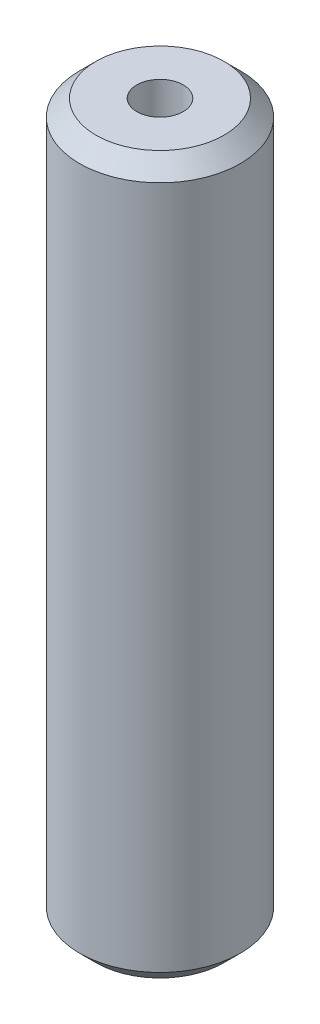
SolidWorks part; units mm, degrees
ref_plane "Front Plane" through (0, 0, 0) normal (0, 0, 1) x (1, 0, 0)
ref_plane "Top Plane" through (0, 0, 0) normal (0, 1, 0) x (1, 0, 0)
ref_plane "Right Plane" through (0, 0, 0) normal (1, 0, 0) x (0, 0, -1)
sketch "Sketch1" plane through (0, 0, 0) normal (0, 1, 0) x (1, 0, 0)
  circle A0 centre (0, 0) radius 5
  dimension "SHAFT_OD" = 10
extrude "Boss-Extrude1" add sketch "Sketch1" along normal blind 44.5572
sketch "Sketch2" plane through (0, 0, 0) normal (0, 1, 0) x (1, 0, 0)
  circle A0 centre (0, 0) radius 1.4435
  dimension "BORE_D" = 2.887
extrude "Cut-Extrude1" cut sketch "Sketch2" along normal through all
chamfer "Chamfer1" distance 1.0191 angle 45 2 edges at (0, 44.5572, 5) (0, 0, 5)
